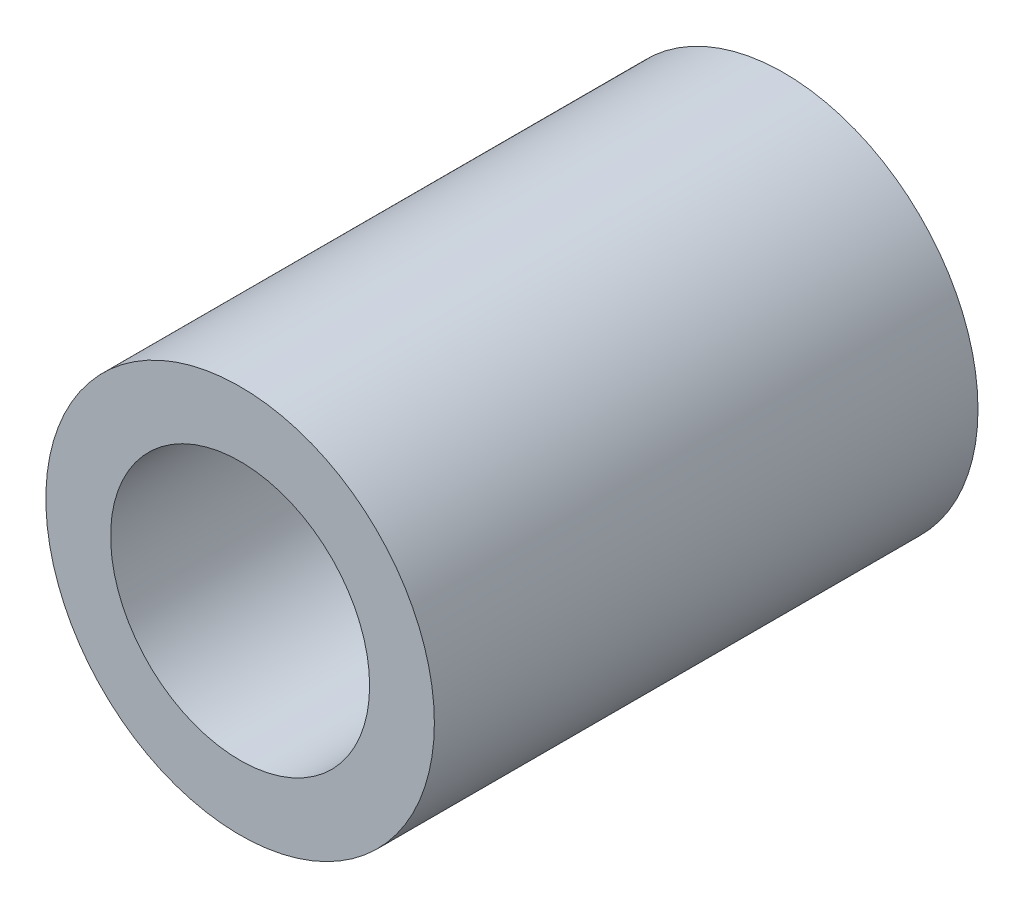
SolidWorks part; units mm, degrees
material "ABS"
ref_plane "Front Plane" through (0, 0, 0) normal (0, 0, 1) x (1, 0, 0)
ref_plane "Top Plane" through (0, 0, 0) normal (0, 1, 0) x (1, 0, 0)
ref_plane "Right Plane" through (0, 0, 0) normal (1, 0, 0) x (0, 0, -1)
sketch "Sketch1" plane through (0, 0, 0) normal (0, 0, 1) x (1, 0, 0)
  circle A0 centre (0, 0) radius 3.175
  circle A1 centre (0, 0) radius 4.7625
  dimension "D1" = 6.35
  dimension "D2" = 9.525
extrude "Boss-Extrude1" add sketch "Sketch1" along normal mid plane 13.3278
